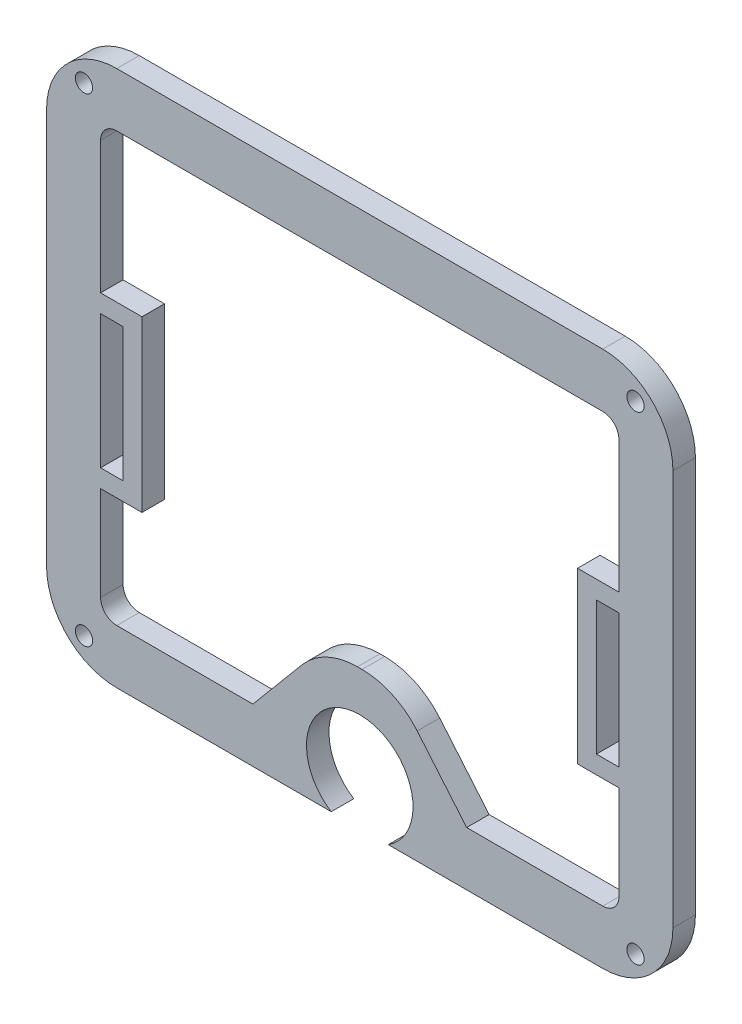
SolidWorks part; units mm, degrees
material "Delrin"
ref_plane "Front Plane" through (0, 0, 0) normal (0, 0, 1) x (1, 0, 0)
ref_plane "Top Plane" through (0, 0, 0) normal (0, 1, 0) x (1, 0, 0)
ref_plane "Right Plane" through (0, 0, 0) normal (1, 0, 0) x (0, 0, -1)
sketch "Sketch1" plane through (0, 0, 0) normal (0, 0, 1) x (1, 0, 0)
  line L0 (-17.145, -18.923) -> (-2.0127, -18.923)
  line L1 (-18.288, 13.97) -> (-18.288, -13.97)
  line L2 (-17.145, -15.113) -> (-7.5425, -15.113)
  line L3 (7.5425, -15.113) -> (17.145, -15.113)
  line L4 (18.288, 13.97) -> (18.288, -13.97)
  line L5 (-1000, 0) -> (49000, 0) construction
  line L7 (2.0127, -18.923) -> (17.145, -18.923)
  line L8 (17.145, 15.113) -> (-17.145, 15.113)
  line L9 (-7.5425, -15.113) -> (-4.0566, -10.9586)
  line L10 (-22.098, 13.97) -> (-22.098, -13.97)
  line L11 (7.5425, -15.113) -> (4.0566, -10.9586)
  line L12 (-0.1651, -9.144) -> (0.1651, -9.144)
  line L13 (22.098, 13.97) -> (22.098, -13.97)
  line L14 (17.145, 18.923) -> (-17.145, 18.923)
  line L18 (0, 12.5532) -> (0, -24.2768) construction
  arc A0 (2.0127, -18.923) -> (-2.0127, -18.923) centre (0, -15.748) ccw
  arc A1 (-17.145, -15.113) -> (-18.288, -13.97) centre (-17.145, -13.97) cw
  arc A2 (-0.1651, -9.144) -> (-4.0566, -10.9586) centre (-0.1651, -14.224) ccw
  arc A3 (18.288, -13.97) -> (17.145, -15.113) centre (17.145, -13.97) cw
  arc A4 (17.145, 15.113) -> (18.288, 13.97) centre (17.145, 13.97) cw
  arc A5 (-17.145, -18.923) -> (-22.098, -13.97) centre (-17.145, -13.97) cw
  arc A6 (22.098, -13.97) -> (17.145, -18.923) centre (17.145, -13.97) cw
  arc A7 (17.145, 18.923) -> (22.098, 13.97) centre (17.145, 13.97) cw
  arc A8 (-17.145, 18.923) -> (-22.098, 13.97) centre (-17.145, 13.97) ccw
  circle A9 centre (-19.4575, 16.891) radius 0.6096
  circle A10 centre (19.4575, 16.891) radius 0.6096
  arc A11 (-17.145, 15.113) -> (-18.288, 13.97) centre (-17.145, 13.97) ccw
  arc A12 (0.1651, -9.144) -> (4.0566, -10.9586) centre (0.1651, -14.224) cw
  circle A13 centre (19.4575, -16.891) radius 0.6096
  circle A14 centre (-19.4575, -16.891) radius 0.6096
  arc A18 (7.5425, -15.113) -> (-7.5425, -15.113) centre (0, -15.748) ccw construction
  point P0 (0, 0)
  dimension "D4" = 3.175
  dimension "D6" = 37.846
  dimension "D7" = 44.196
  dimension "D8" = 3.81
  dimension "D9" = 6.604
  dimension "D5" = 1.2192
  dimension "D2" = 4.953
  dimension "D3" = 7.5184
  dimension "D10" = 5.08
  dimension "D11" = 5.08
  dimension "D12" = 16.891
  dimension "D13" = 19.4575
extrude "Boss-Extrude1" add sketch "Sketch1" along normal blind 1.5875
sketch "Sketch2" plane through (-18.288, 0, 0) normal (1, 0, 0) x (0, 0, -1)
  line L0 (0, 3.3744) -> (-1.5875, 3.3744)
  line L1 (0, -6.0467) -> (-1.5875, -6.0467) construction
  line L2 (-1.5875, -15.113) -> (0, -15.113)
  line L3 (-1.5875, -15.113) -> (0, -15.113) construction
  line L4 (0, -13.97) -> (0, 13.97)
  line L5 (0, 13.97) -> (-1.5875, 13.97)
  line L6 (-1.5875, 13.97) -> (-1.5875, -13.97)
  line L7 (0, 13.97) -> (-1.5875, 13.97)
  line L8 (0, -13.97) -> (0, 4.6444)
  line L9 (-1.5875, -15.113) -> (-1.5875, -7.3167)
  line L10 (-1.5875, 4.6444) -> (-1.5875, -13.97)
  line L11 (-1.5875, -13.97) -> (0, -13.97)
  line L12 (0, -15.113) -> (0, -7.3167)
  line L13 (0, 4.6444) -> (-1.5875, 4.6444)
  line L14 (-1.5875, 3.3744) -> (-1.5875, -6.6447)
  line L15 (-1.5875, 4.6444) -> (-1.5875, 3.3744)
  line L16 (0, 3.3744) -> (0, 4.6444)
  line L17 (0, -7.9147) -> (0, 1.4693)
  line L18 (-1.5875, -7.9147) -> (-1.5875, -6.6447)
  line L19 (0, -6.0467) -> (-1.5875, -6.0467)
  line L21 (0, -7.3167) -> (-1.5875, -7.3167)
  line L22 (0, -7.3167) -> (0, -13.97)
  line L23 (-1.5875, -7.3167) -> (-1.5875, -13.97)
  line L24 (48.0325, 2.7172) -> (-35.7347, 3.8634) construction
  line L25 (8.7621, 1.3494) -> (-32.627, 1.9157) construction
  line L28 (-1.5875, -13.97) -> (0, -13.97)
  line L29 (47.4507, -9.8102) -> (-36.0622, -3.1864) construction
  line M5 (0, -13.97) -> (0, 13.97)
  line M7 (-1.5875, 13.97) -> (-1.5875, -13.97)
  dimension "D1" = 0
  dimension "D2" = 1.27
  dimension "D4" = 1.27
extrude "Boss-Extrude2" add sketch "Sketch2" along normal blind 2.921 contours L13 L10 L0 M5 | L19 L17 L8 L0 L10 M7 | L21 L8 L19 L18 M5 M7 region at (-18.288, -1.3361, 0.7937) region at (-18.288, 4.0094, 0.7937) region at (-18.288, -6.6817, 0.7937)
extrude "Cut-Extrude1" cut sketch "Sketch2<3>" along normal blind 1.5875 contours L19 L8 L10 | L19 L17 L0 M5 M7 region at (-18.288, -1.3361, 0.7937)
sketch "Sketch2<3>" plane through (-18.288, 0, 0) normal (1, 0, 0) x (0, 0, -1) same geometry as "Sketch2"
mirror "Mirror1" about plane through (0, 0, 0) normal (1, 0, 0) of "Cut-Extrude1", "Boss-Extrude2"
